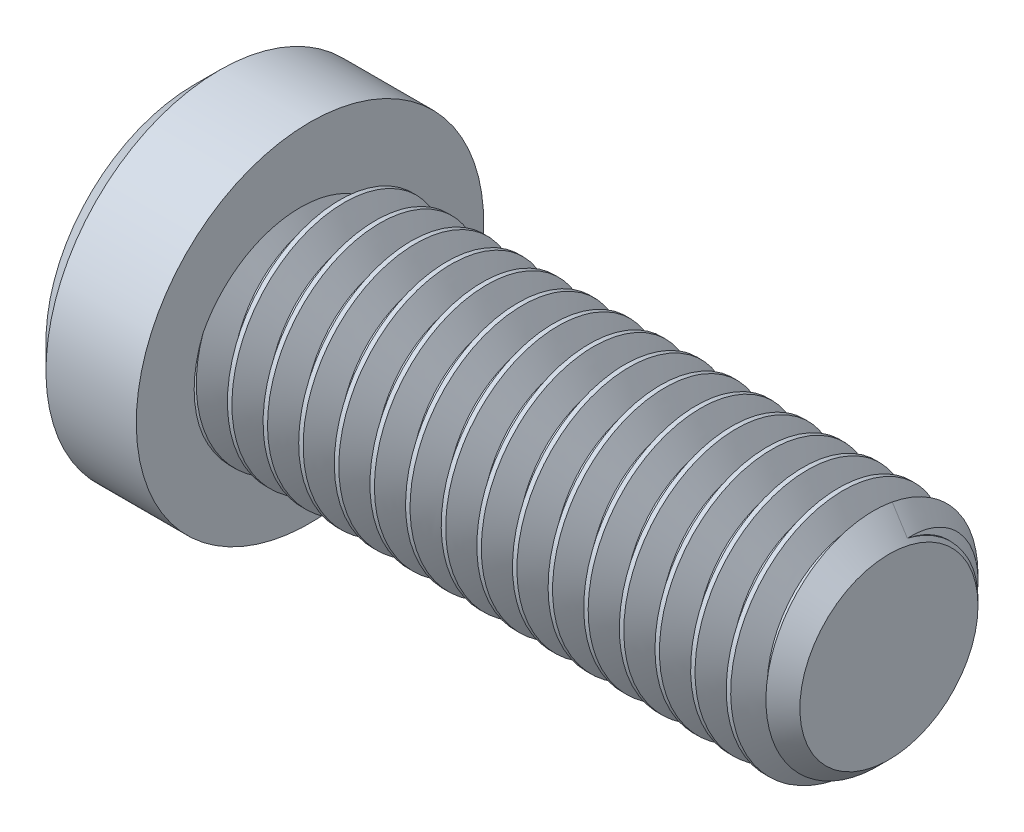
SolidWorks part; units mm, degrees
material "Plain Carbon Steel"
ref_plane "Front Plane" through (0, 0, 0) normal (0, 0, 1) x (1, 0, 0)
ref_plane "Top Plane" through (0, 0, 0) normal (0, 1, 0) x (1, 0, 0)
ref_plane "Right Plane" through (0, 0, 0) normal (1, 0, 0) x (0, 0, -1)
sketch "Sketch1" plane through (0, 0, 0) normal (0, 0, 1) x (1, 0, 0)
  line L0 (15.875, 0) -> (-15.875, 0) construction
  line L1 (15.875, 6.35) -> (15.875, -6.35) construction
  line L2 (-15.875, 9.525) -> (-15.875, -9.525) construction
  line L3 (-15.875, 9.525) -> (-20.828, 9.525) construction
  line L4 (-20.828, 9.525) -> (-22.225, 8.128) construction
  line L5 (-22.225, 8.128) -> (-22.225, -8.128) construction
  line L6 (-22.225, -8.128) -> (-20.828, -9.525) construction
  line L7 (-20.828, -9.525) -> (-15.875, -9.525) construction
  point P7 (-18.3896, 0)
  point P12 (8.0596, -6.35)
  dimension "D1" = 45
  dimension "D2" = 7.8154
  dimension "Dec." = 12.7
  dimension "Length" = 31.75
  dimension "Head Dia" = 19.05
  dimension "Head Height" = 6.35
  dimension "Hex Depth" = 3.8354
  dimension "Chamfer" = 1.397
ref_plane "Plane1" through (15.875, 0, 0) normal (1, 0, 0) x (0, 0, -1)
ref_plane "Plane2" through (-22.225, 0, 0) normal (1, 0, 0) x (0, 0, -1)
sketch "Sketch2" plane through (15.875, 0, 0) normal (1, 0, 0) x (0, 0, -1)
  circle A0 centre (0, 0) radius 6.35
extrude "Boss-Extrude1" add sketch "Sketch2" against normal up to vertex (31.75 mm away) up to point (-15.875, 0, 0)
sketch "Sketch3" plane through (15.875, 0, 0) normal (1, 0, 0) x (0, 0, -1)
  circle A0 centre (0, 0) radius 6.35 construction
  circle A1 centre (0, 0) radius 6.35
curve "Helix/Spiral1" pitch 1.9538 height 33.7038 radius 6.35 centre (15.875, 0, 0) axis (-1, 0, 0) start towards (0, 1, 0) parameters "Pitch"=1.9538
chamfer "Chamfer1" distance 1.4654 angle 45 1 edges at (15.875, 0, -6.35)
sketch "Sketch5" plane through (0, 0, 0) normal (0, 0, 1) x (1, 0, 0)
  line L0 (15.0202, 6.35) -> (16.7298, 6.35)
  line L1 (16.7298, 6.35) -> (15.9971, 5.0809)
  line L2 (15.9971, 5.0809) -> (15.7529, 5.0809)
  line L3 (15.7529, 5.0809) -> (15.0202, 6.35)
  line L4 (15.875, 5.0809) -> (15.875, 6.35) construction
  line L5 (15.3865, 5.7155) -> (16.3635, 5.7155) construction
  dimension "D1" = 60
  dimension "D2" = 0.9769
  dimension "D3" = 0.2442
sweep "Cut-Sweep1" cut profiles "Sketch5" path "Helix/Spiral1"
sketch "Sketch4" plane through (-22.225, 0, 0) normal (1, 0, 0) x (0, 0, -1)
  line L0 (-9.525, 0.7937) -> (9.525, 0.7937) construction
  line L1 (0, 3.6662) -> (-3.175, 1.8331)
  line L2 (-3.175, 1.8331) -> (-3.175, -1.8331)
  line L3 (-3.175, -1.8331) -> (0, -3.6662)
  line L4 (0, -3.6662) -> (3.175, -1.8331)
  line L5 (3.175, -1.8331) -> (3.175, 1.8331)
  line L6 (3.175, 1.8331) -> (0, 3.6662)
  line L7 (0, 0) -> (0, 0.7937) construction
  circle A0 centre (0, 0) radius 3.175 construction
  dimension "D1" = 19.05
  dimension "Hex Size" = 6.35
  dimension "D2" = 0.7937
sketch "Sketch6" plane through (0, 0, 0) normal (0, 0, 1) x (1, 0, 0)
  line L0 (-20.828, 9.525) -> (-22.225, 8.128) construction
  line L1 (-15.875, 9.525) -> (-20.828, 9.525) construction
  line L2 (-15.875, 9.525) -> (-15.875, -9.525) construction
  line L3 (-22.225, 8.128) -> (-22.225, -8.128) construction
  line L4 (-20.828, 9.525) -> (-22.225, 8.128)
  line L5 (-15.875, 9.525) -> (-20.828, 9.525)
  line L6 (-15.875, 9.525) -> (-15.875, 0)
  line L7 (-22.225, 8.128) -> (-22.225, 0)
  line L8 (-15.875, 0) -> (-22.225, 0) construction
  line L9 (-15.875, 0) -> (-22.225, 0)
revolve "Revolve1" add sketch "Sketch6" angle 360 about L8
extrude "Cut-Extrude1" cut sketch "Sketch4" along normal up to vertex (3.8354 mm away) up to point (-18.3896, 0, 0)
sketch "Sketch8" plane through (-22.225, 0, 0) normal (-1, 0, 0) x (0, 0, 1)
  circle A1 centre (0, 0) radius 3.6662
extrude "Cut-Extrude2" cut sketch "Sketch8" against normal through all draft 45
equation "\"D3@Helix/Spiral1\" = \"Length@Sketch1\"+\"Pitch@Helix/Spiral1\""
equation "\"D3@Sketch5\" = \"Pitch@Helix/Spiral1\"*.125"
equation "\"D2@Sketch5\" = \"Pitch@Helix/Spiral1\"*.50"
equation "\"D1@Chamfer1\" = \"Pitch@Helix/Spiral1\"*.75"
equation "\"D2@Sketch1\" = \"Pitch@Helix/Spiral1\"*4"
equation "\"D1@Sketch4\" = \"Head Dia@Sketch1\""
